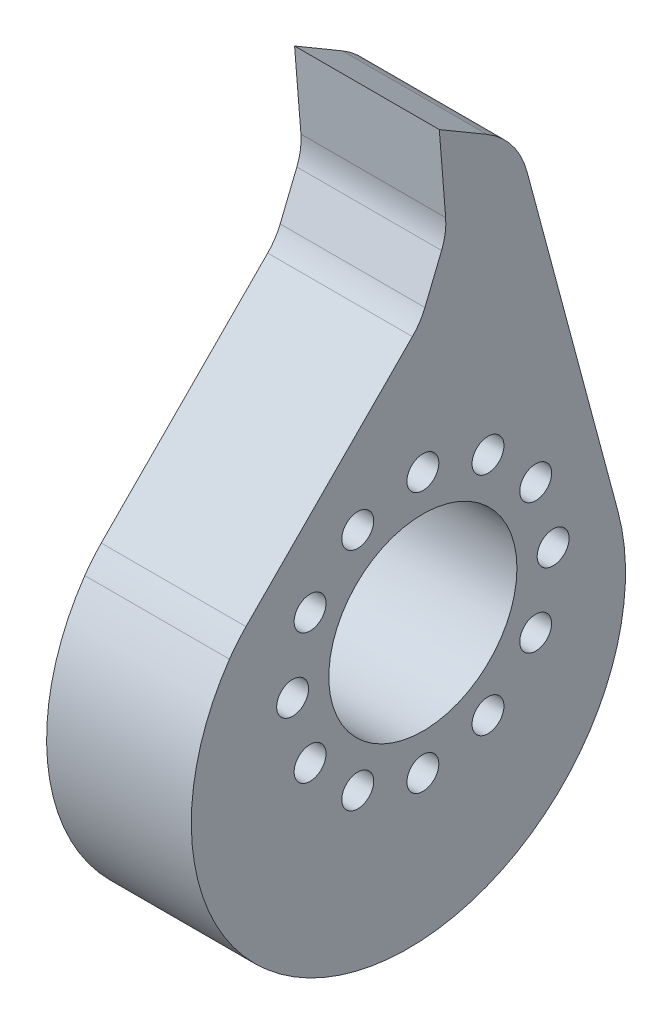
SolidWorks part; units mm, degrees
ref_plane "Front Plane" through (0, 0, 0) normal (0, 0, 1) x (1, 0, 0)
ref_plane "Top Plane" through (0, 0, 0) normal (0, 1, 0) x (1, 0, 0)
ref_plane "Right Plane" through (0, 0, 0) normal (1, 0, 0) x (0, 0, -1)
other "Center of Mass"
sketch "Sketch1" plane through (0, 0, 0) normal (1, 0, 0) x (0, 0, -1)
  line L0 (18.402, 4.9264) -> (9.6079, 37.7759)
  line L1 (9.6079, 37.7759) -> (2.7094, 41.8274)
  line L2 (2.7094, 41.8274) -> (3.3664, 33.6514)
  line L3 (3.3664, 33.6514) -> (1.0669, 27.9939)
  line L4 (1.0669, 27.9939) -> (-14.8407, 11.9439)
  circle A0 centre (0, 0) radius 19.05
  dimension "D1" = 38.1
extrude "Boss-Extrude1" add sketch "Sketch1" along normal blind 12.7 contours A0 | A0 region at (0, 25.2483, -6.1364) region at (0, -0.0031, -0.0031)
fillet "Fillet1" radius 7.62 1 edges at (6.35, 37.7759, -9.6079)
fillet "Fillet2" radius 5.08 1 edges at (6.35, 27.9939, -1.0669)
fillet "Fillet3" radius 5.08 1 edges at (6.35, 33.6514, -3.3664)
fillet "Fillet4" radius 12.7 1 edges at (6.35, 11.9439, 14.8407)
sketch "Sketch2" plane through (12.7, 0, 0) normal (1, 0, 0) x (0, 0, -1)
  circle A0 centre (1.27, 5.08) radius 8.255
  dimension "D3" = 16.51
  dimension "D1" = 1.27
  dimension "D2" = 5.08
extrude "Cut-Extrude1" cut sketch "Sketch2" against normal through all
sketch "Sketch3" plane through (12.7, 0, 0) normal (1, 0, 0) x (0, 0, -1)
  circle A0 centre (1.27, 16.51) radius 1.4
  circle A1 centre (1.27, 5.08) radius 8.255 construction
  circle A2 centre (1.27, 5.08) radius 8.255
  circle A3 centre (6.985, 14.9787) radius 1.4
  circle A4 centre (11.1687, 10.795) radius 1.4
  circle A5 centre (12.7, 5.08) radius 1.4
  circle A6 centre (11.1687, -0.635) radius 1.4
  circle A7 centre (6.985, -4.8187) radius 1.4
  circle A8 centre (1.27, -6.35) radius 1.4
  circle A9 centre (-4.445, -4.8187) radius 1.4
  circle A10 centre (-8.6287, -0.635) radius 1.4
  circle A11 centre (-10.16, 5.08) radius 1.4
  circle A12 centre (-8.6287, 10.795) radius 1.4
  circle A13 centre (-4.445, 14.9787) radius 1.4
  point P22 (1.27, 5.08)
  dimension "D1" = 11.43
  dimension "D2" = 2.8
  dimension "D3" = 12
extrude "Cut-Extrude2" cut sketch "Sketch3" against normal through all contours A8 | A7 | A6 | A5 | A4 | A3 | A0 | A13 | A12 | A11 | A10 | A9 | A9 region at (12.7, 16.51, -1.27) region at (12.7, 14.9787, -6.985) region at (12.7, 10.795, -11.1687) region at (12.7, 5.08, -12.7) region at (12.7, -0.635, -11.1687) region at (12.7, -4.8187, -6.985) region at (12.7, -6.35, -1.27) region at (12.7, -4.8187, 4.445) region at (12.7, -0.635, 8.6287) region at (12.7, 5.08, 10.16) region at (12.7, 10.795, 8.6287) region at (12.7, 14.9787, 4.445)
